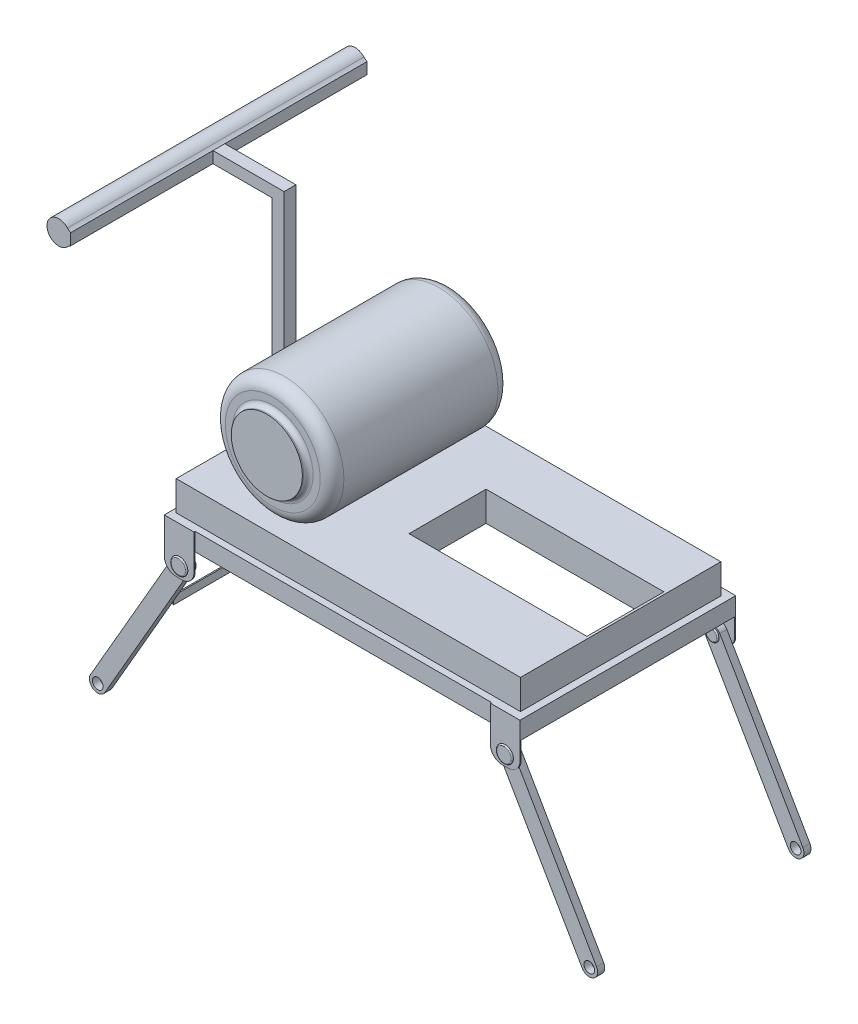
SolidWorks part; units mm, degrees
ref_plane "Front Plane" through (0, 0, 0) normal (0, 0, 1) x (1, 0, 0)
ref_plane "Top Plane" through (0, 0, 0) normal (0, 1, 0) x (1, 0, 0)
ref_plane "Right Plane" through (0, 0, 0) normal (1, 0, 0) x (0, 0, -1)
sketch "Sketch1" plane through (0, 0, 0) normal (0, 0, 1) x (1, 0, 0)
  line L1 (-101.9566, 25.9987) -> (198.0434, 25.9987)
  line L2 (-101.9566, 25.9987) -> (-101.9566, 10.9987)
  line L3 (-101.9566, 10.9987) -> (198.0434, 10.9987)
  line L4 (198.0434, 25.9987) -> (198.0434, 10.9987)
extrude "Boss-Extrude1" add sketch "Sketch1" against normal blind 180
sketch "Sketch2" plane through (0, 25.9987, 0) normal (0, 1, 0) x (1, 0, 0)
  line L1 (-90.6747, 169.789) -> (185.7185, 169.789)
  line L2 (-90.6747, 169.789) -> (-90.6747, 10.7325)
  line L3 (-90.6747, 10.7325) -> (185.7185, 10.7325)
  line L4 (185.7185, 169.789) -> (185.7185, 10.7325)
extrude "Cut-Extrude1" cut sketch "Sketch2" against normal blind 180
sketch "Sketch3" plane through (0, 25.9987, 0) normal (0, 1, 0) x (1, 0, 0)
  line L1 (-96.4111, 174.4824) -> (191.9764, 174.4824)
  line L2 (-96.4111, 174.4824) -> (-96.4111, 5.5176)
  line L3 (-96.4111, 5.5176) -> (191.9764, 5.5176)
  line L4 (191.9764, 174.4824) -> (191.9764, 5.5176)
extrude "Boss-Extrude2" add sketch "Sketch3" along normal blind 25
sketch "Sketch4" plane through (0, 0, 0) normal (0, 0, 1) x (1, 0, 0)
  line L0 (173.0434, 25.9987) -> (173.0434, -4.0013)
  line L1 (-101.9566, 25.9987) -> (-76.9566, 25.9987)
  line L2 (-101.9566, 25.9987) -> (-101.9566, -4.0013)
  line L3 (-91.9566, -14.0013) -> (-86.9566, -14.0013)
  line L4 (-76.9566, 25.9987) -> (-76.9566, -4.0013)
  line L5 (198.0434, 25.9987) -> (198.0434, -4.0013)
  line L6 (173.0434, 25.9987) -> (198.0434, 25.9987)
  line L7 (183.0434, -14.0013) -> (188.0434, -14.0013)
  arc A0 (173.0434, -4.0013) -> (183.0434, -14.0013) centre (183.0434, -4.0013) ccw
  arc A1 (198.0434, -4.0013) -> (188.0434, -14.0013) centre (188.0434, -4.0013) cw
  arc A2 (-91.9566, -14.0013) -> (-101.9566, -4.0013) centre (-91.9566, -4.0013) cw
  arc A3 (-86.9566, -14.0013) -> (-76.9566, -4.0013) centre (-86.9566, -4.0013) ccw
  dimension "D1" = 10
extrude "Boss-Extrude3" add sketch "Sketch4" along normal blind 1
sketch "Sketch5" plane through (0, 0, -180) normal (0, 0, -1) x (-1, 0, 0)
  line L0 (-173.0434, 25.9987) -> (-173.0434, -4.0013)
  line L1 (76.5767, 26.0088) -> (101.5767, 26.0088)
  line L2 (76.5767, 26.0088) -> (76.5767, -3.9912)
  line L3 (86.5767, -13.9912) -> (91.5767, -13.9912)
  line L4 (101.5767, 26.0088) -> (101.5767, -3.9912)
  line L5 (-188.0434, -14.0013) -> (-183.0434, -14.0013)
  line L6 (-198.0434, 25.9987) -> (-173.0434, 25.9987)
  line L7 (-198.0434, 25.9987) -> (-198.0434, -4.0013)
  arc A0 (-188.0434, -14.0013) -> (-198.0434, -4.0013) centre (-188.0434, -4.0013) cw
  arc A1 (-183.0434, -14.0013) -> (-173.0434, -4.0013) centre (-183.0434, -4.0013) ccw
  arc A2 (91.5767, -13.9912) -> (101.5767, -3.9912) centre (91.5767, -3.9912) ccw
  arc A3 (76.5767, -3.9912) -> (86.5767, -13.9912) centre (86.5767, -3.9912) ccw
  dimension "D1" = 10
  dimension "D2" = 10
extrude "Boss-Extrude4" add sketch "Sketch5" along normal blind 1
sketch "Sketch6" plane through (0, 0, 1) normal (0, 0, 1) x (1, 0, 0)
  circle A0 centre (-89.0767, -4.971) radius 5
  circle A1 centre (185.5434, -4.971) radius 5
extrude "Cut-Extrude2" cut sketch "Sketch6" against normal blind 200
sketch "Sketch7" plane through (0, 0, 0) normal (0, 0, -1) x (-1, 0, 0)
  line L0 (-185.5434, 10.9891) -> (-185.5434, -123.4318) construction
  line L1 (89.0767, 26.0088) -> (89.0767, -123.4318) construction
  line L2 (101.5767, 26.0088) -> (76.5767, 26.0088) construction
  line L3 (-185.5434, -4.971) -> (-255.5434, -126.2145) construction
  line L4 (-179.4812, -8.471) -> (-249.4812, -129.7145)
  line L5 (-191.6056, -1.471) -> (-261.6056, -122.7145)
  line L6 (89.0767, -4.971) -> (159.0767, -126.2145) construction
  line L7 (95.1389, -1.471) -> (165.1389, -122.7145)
  line L8 (83.0145, -8.471) -> (153.0145, -129.7145)
  line L9 (-185.5434, -123.4318) -> (-185.5434, -171.992) construction
  line L10 (89.0767, -116.656) -> (89.0767, -155.8943) construction
  arc A0 (-179.4812, -8.471) -> (-191.6056, -1.471) centre (-185.5434, -4.971) ccw
  arc A1 (-261.6056, -122.7145) -> (-249.4812, -129.7145) centre (-255.5434, -126.2145) ccw
  arc A2 (95.1389, -1.471) -> (83.0145, -8.471) centre (89.0767, -4.971) ccw
  arc A3 (153.0145, -129.7145) -> (165.1389, -122.7145) centre (159.0767, -126.2145) ccw
  circle A4 centre (-185.5434, -4.971) radius 4.8
  circle A5 centre (-255.5434, -126.2145) radius 4.5
  circle A6 centre (89.0767, -4.971) radius 4.5
  circle A7 centre (159.0767, -126.2145) radius 4.5
  point P9 (-220.5434, -65.5928)
  point P17 (124.0767, -65.5928)
  dimension "D2" = 7
  dimension "D5" = 7
  dimension "D1" = 140
  dimension "D3" = 140
  dimension "D4" = 70
  dimension "D6" = 70
extrude "Boss-Extrude5" add sketch "Sketch7" along normal blind 6
sketch "Sketch8" plane through (0, 0, -180) normal (0, 0, 1) x (1, 0, 0)
  line L0 (-89.0767, -4.971) -> (-159.0767, -126.2145) construction
  line L1 (-83.0145, -8.471) -> (-153.0145, -129.7145)
  line L2 (-95.1389, -1.471) -> (-165.1389, -122.7145)
  line L3 (185.5434, -4.971) -> (255.5434, -126.2145) construction
  line L4 (191.6056, -1.471) -> (261.6056, -122.7145)
  line L5 (179.4812, -8.471) -> (249.4812, -129.7145)
  arc A0 (-83.0145, -8.471) -> (-95.1389, -1.471) centre (-89.0767, -4.971) ccw
  arc A1 (-165.1389, -122.7145) -> (-153.0145, -129.7145) centre (-159.0767, -126.2145) ccw
  arc A2 (191.6056, -1.471) -> (179.4812, -8.471) centre (185.5434, -4.971) ccw
  arc A3 (249.4812, -129.7145) -> (261.6056, -122.7145) centre (255.5434, -126.2145) ccw
  circle A4 centre (-89.0767, -4.971) radius 4.5
  circle A5 centre (-159.0767, -126.2145) radius 4.5
  circle A6 centre (185.5434, -4.971) radius 4.5
  circle A7 centre (255.5434, -126.2145) radius 4.5
  point P4 (-124.0767, -65.5928)
  point P9 (220.5434, -65.5928)
  dimension "D1" = 7
  dimension "D2" = 7
extrude "Boss-Extrude6" add sketch "Sketch8" along normal blind 6
sketch "Sketch15" plane through (0, 0, 1) normal (0, 0, 1) x (1, 0, 0)
  circle A0 centre (185.5434, -4.971) radius 7
  circle A1 centre (-89.0767, -4.971) radius 7
extrude "Boss-Extrude13" add sketch "Sketch15" along normal blind 1
fillet "Fillet2" radius 1 1 edges at (-82.0767, -4.971, 2)
fillet "Fillet3" radius 1 1 edges at (192.5434, -4.971, 2)
sketch "Sketch16" plane through (0, 0, -181) normal (0, 0, -1) x (-1, 0, 0)
  circle A0 centre (-185.5434, -4.971) radius 7.5
  circle A1 centre (89.0767, -4.971) radius 7.5
extrude "Boss-Extrude14" add sketch "Sketch16" along normal blind 1
fillet "Fillet4" radius 1 2 edges at (-96.5767, -4.971, -182) (178.0434, -4.971, -182)
sketch "Sketch17" plane through (0, 0, -6) normal (0, 0, -1) x (-1, 0, 0)
  circle A0 centre (89.0767, -4.971) radius 5.5
  circle A1 centre (-185.5434, -4.971) radius 5.5
extrude "Boss-Extrude15" add sketch "Sketch17" along normal blind 1
fillet "Fillet5" radius 1 2 edges at (-94.5767, -4.971, -7) (180.0434, -4.971, -7)
sketch "Sketch18" plane through (0, 0, -174) normal (0, 0, 1) x (1, 0, 0)
  circle A0 centre (-89.0767, -4.971) radius 5.5
  circle A1 centre (185.5434, -4.971) radius 5.5
extrude "Boss-Extrude16" add sketch "Sketch18" along normal blind 1
fillet "Fillet6" radius 1 2 edges at (191.0434, -4.971, -173) (-83.5767, -4.971, -173)
sketch "Sketch25" plane through (-96.4111, 0, 0) normal (-1, 0, 0) x (0, 0, 1)
  line L1 (-174.4824, 50.9987) -> (-5.5176, 50.9987)
  line L2 (-174.4824, 50.9987) -> (-174.4824, 25.9987)
  line L3 (-174.4824, 25.9987) -> (-5.5176, 25.9987)
  line L4 (-5.5176, 50.9987) -> (-5.5176, 25.9987)
extrude "Boss-Extrude22" add sketch "Sketch25" along normal blind 2
sketch "Sketch28" plane through (0, 50.9987, 0) normal (0, 1, 0) x (1, 0, 0)
  line L0 (-101.9566, 89.5) -> (0, 89.5) construction
  line L1 (-101.9566, 180) -> (-101.9566, -1) construction
  line L2 (-97.5438, 174.4824) -> (-97.5438, 5.5176) construction
  line L3 (-97.5438, 95.6458) -> (-87.5438, 95.6458)
  line L4 (-97.5438, 95.6458) -> (-97.5438, 85.6458)
  line L5 (-97.5438, 85.6458) -> (-87.5438, 85.6458)
  line L6 (-87.5438, 95.6458) -> (-87.5438, 85.6458)
extrude "Boss-Extrude25" add sketch "Sketch28" along normal blind 175
sketch "Sketch33" plane through (0, 50.9987, 0) normal (0, 1, 0) x (1, 0, 0)
  line L1 (-74.5778, 103.9969) -> (-57.1258, 103.9969)
  line L2 (-74.5778, 103.9969) -> (-74.5778, 72.9237)
  line L3 (-74.5778, 72.9237) -> (-57.1258, 72.9237)
  line L4 (-57.1258, 103.9969) -> (-57.1258, 72.9237)
extrude "Boss-Extrude27" add sketch "Sketch33" along normal blind 15
fillet "Fillet7" radius 5 2 edges at (-57.1258, 65.9987, -88.4603) (-74.5778, 65.9987, -88.4603)
sketch "Sketch34" plane through (0, 0, -72.9237) normal (0, 0, 1) x (1, 0, 0)
  circle A0 centre (-66.5607, 58.1389) radius 2
extrude "Extrude-Thin3" add sketch "Sketch34" along normal blind 5 and the other way blind 35 thin thin type one direction reverse wall 0.5
sketch "Sketch35" plane through (0, 50.9987, 0) normal (0, 1, 0) x (1, 0, 0)
  line L0 (-57.1258, 72.9237) -> (-57.1258, 103.9969) construction
  line L1 (-57.1258, 90.8853) -> (-54.2932, 90.8853)
  line L2 (-57.1258, 90.8853) -> (-57.1258, 86.8333)
  line L3 (-57.1258, 86.8333) -> (-54.2932, 86.8333)
  line L4 (-54.2932, 90.8853) -> (-54.2932, 86.8333)
  line L5 (-74.5778, 103.9969) -> (-74.5778, 72.9237) construction
  line L6 (-74.5778, 90.8853) -> (-77.3478, 90.8853)
  line L7 (-74.5778, 90.8853) -> (-74.5778, 86.8333)
  line L8 (-74.5778, 86.8333) -> (-77.3478, 86.8333)
  line L9 (-77.3478, 90.8853) -> (-77.3478, 86.8333)
  circle A0 centre (-75.9628, 88.8593) radius 0.8
  circle A1 centre (-55.6883, 88.8593) radius 0.8
extrude "Boss-Extrude28" add sketch "Sketch35" along normal blind 0.5
sketch "Sketch36" plane through (-87.5438, 0, 0) normal (1, 0, 0) x (0, 0, -1)
  circle A0 centre (90.399, 55.2883) radius 1.5
extrude "Boss-Extrude29" add sketch "Sketch36" along normal blind 14
ref_plane "Plane1" through (0, 0, -15.5176) normal (0, 0, 1) x (1, 0, 0)
sketch "Sketch38" plane through (0, 0, -15.5176) normal (0, 0, 1) x (1, 0, 0)
  circle A0 centre (-26.9773, 101.3217) radius 50
extrude "Boss-Extrude31" add sketch "Sketch38" against normal blind 150
sketch "Sketch39" plane through (0, 0, -15.5176) normal (0, 0, 1) x (1, 0, 0)
  circle A0 centre (-26.9773, 101.3217) radius 30
extrude "Boss-Extrude32" add sketch "Sketch39" along normal blind 5
sketch "Sketch40" plane through (0, 0, -165.5176) normal (0, 0, -1) x (-1, 0, 0)
  circle A0 centre (26.9773, 101.3217) radius 30
extrude "Boss-Extrude33" add sketch "Sketch40" along normal blind 5
fillet "Fillet8" radius 10 2 edges at (23.0227, 101.3217, -165.5176) (23.0227, 101.3217, -15.5176)
fillet "Fillet9" radius 4 2 edges at (-56.9773, 101.3217, -170.5176) (3.0227, 101.3217, -15.5176)
sketch "Sketch41" plane through (0, 50.9987, 0) normal (0, 1, 0) x (1, 0, 0)
  line L1 (39.9803, 128.4952) -> (189.9803, 128.4952)
  line L2 (39.9803, 128.4952) -> (39.9803, 63.4952)
  line L3 (39.9803, 63.4952) -> (189.9803, 63.4952)
  line L4 (189.9803, 128.4952) -> (189.9803, 63.4952)
extrude "Cut-Extrude5" cut sketch "Sketch41" against normal blind 40
sketch "Sketch43" plane through (-97.5438, 0, 0) normal (-1, 0, 0) x (0, 0, 1)
  line L0 (-85.6458, 225.9987) -> (-85.6458, 50.9987) construction
  line L1 (-95.6458, 225.9987) -> (-85.6458, 225.9987)
  line L2 (-95.6458, 225.9987) -> (-95.6458, 216.3934)
  line L3 (-95.6458, 216.3934) -> (-85.6458, 216.3934)
  line L4 (-85.6458, 225.9987) -> (-85.6458, 216.3934)
extrude "Boss-Extrude34" add sketch "Sketch43" along normal blind 50
sketch "Sketch44" plane through (0, 0, -85.6458) normal (0, 0, 1) x (1, 0, 0)
  line L0 (-147.5438, 225.9987) -> (-147.5438, 216.3934)
  arc A0 (-150.213, 227.9975) -> (-149.5596, 215.175) centre (-157.5438, 221.196) ccw
  arc A1 (-147.5438, 225.9987) -> (-150.213, 227.9975) centre (-140.5348, 238.1403) cw
  arc A2 (-147.5438, 216.3934) -> (-150.213, 214.3946) centre (-145.9615, 211.4988) ccw
  line M4 (-147.5438, 225.9987) -> (-147.5438, 216.3934)
extrude "Boss-Extrude35" add sketch "Sketch44" along normal blind 120 and the other way blind 130 contours A2 A1 A0 M4 region at (-157.3903, 221.2031, -85.6458)
ref_plane "Plane2" through (-167.5438, 0, 0) normal (-1, 0, 0) x (0, 0, 1)
sketch "Sketch45" plane through (-167.5438, 0, 0) normal (-1, 0, 0) x (0, 0, 1)
  circle A0 centre (-188.4767, 221.0378) radius 3
  circle A1 centre (-164.9119, 221.0378) radius 3
  circle A2 centre (-141.0743, 221.0378) radius 3
  circle A3 centre (-115.3406, 221.0378) radius 3
  circle A4 centre (-86.8981, 221.0378) radius 3
  circle A5 centre (-56.8303, 221.0378) radius 3
  circle A6 centre (-26.7625, 221.0378) radius 3
  circle A7 centre (2.2217, 221.0378) radius 3
extrude "Cut-Extrude6" cut sketch "Sketch45" against normal blind 5
sketch "Sketch46" plane through (-101.9566, 0, 0) normal (-1, 0, 0) x (0, 0, 1)
  line L0 (-174, -1.471) -> (-174, -122.7145) construction
  line L1 (-174, -36.0486) -> (-6, -36.0486)
  line L2 (-174, -36.0486) -> (-174, -42.6721)
  line L3 (-174, -42.6721) -> (-6, -42.6721)
  line L4 (-6, -36.0486) -> (-6, -42.6721)
  line L5 (-6, -122.7145) -> (-6, -1.471) construction
extrude "Boss-Extrude36" add sketch "Sketch46" against normal blind 1
sketch "Sketch47" plane through (-101.9566, 0, 0) normal (-1, 0, 0) x (0, 0, 1)
  line L0 (-174, -42.6721) -> (-6, -42.6721) construction
  line L1 (-93.4639, -42.6721) -> (-80.4639, -42.6721)
  line L2 (-93.4639, -42.6721) -> (-93.4639, -36.0486)
  line L3 (-93.4639, -36.0486) -> (-80.4639, -36.0486)
  line L4 (-80.4639, -42.6721) -> (-80.4639, -36.0486)
  line L5 (-6, -36.0486) -> (-174, -36.0486) construction
extrude "Boss-Extrude37" add sketch "Sketch47" along normal blind 15
